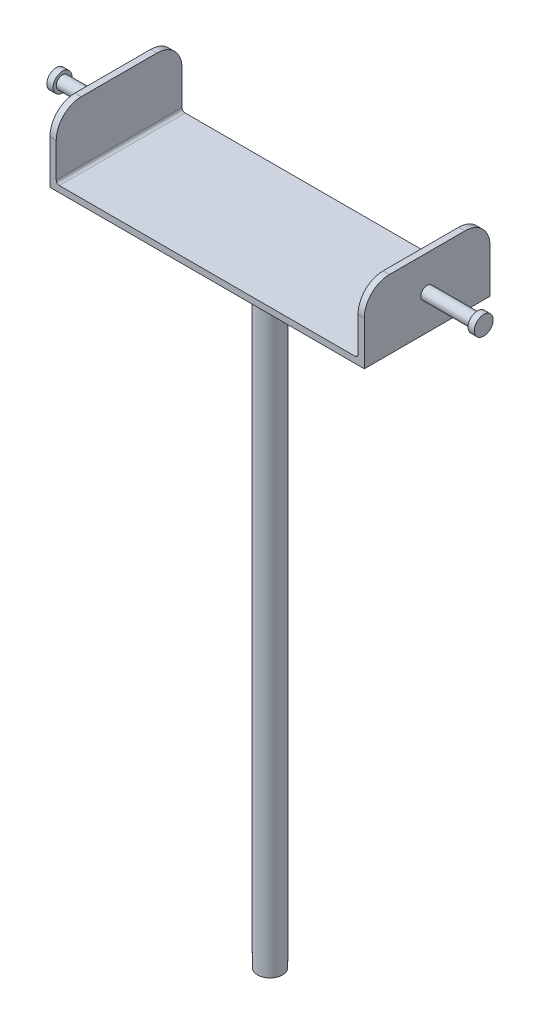
SolidWorks part; units mm, degrees
material "1060 Alloy"
ref_plane "Front Plane" through (0, 0, 0) normal (0, 0, 1) x (1, 0, 0)
ref_plane "Top Plane" through (0, 0, 0) normal (0, 1, 0) x (1, 0, 0)
ref_plane "Right Plane" through (0, 0, 0) normal (1, 0, 0) x (0, 0, -1)
sketch "Sketch1" plane through (0, 0, 0) normal (0, 1, 0) x (1, 0, 0)
  line L0 (-125, 50) -> (125, -50) construction
  line L1 (-125, 50) -> (125, 50)
  line L2 (-125, 50) -> (-125, -50)
  line L3 (-125, -50) -> (125, -50)
  line L4 (125, 50) -> (125, -50)
  dimension "D1" = 250
  dimension "D2" = 100
extrude "Boss-Extrude1" add sketch "Sketch1" along normal blind 5
sketch "Sketch2" plane through (0, 5, 0) normal (0, 1, 0) x (1, 0, 0)
  line L0 (-125, -50) -> (125, -50) construction
  line L1 (-125, 50) -> (-120, 50)
  line L2 (-125, 50) -> (-125, -50)
  line L3 (-125, -50) -> (-120, -50)
  line L4 (-120, 50) -> (-120, -50)
  line L5 (0, 50) -> (0, 56.6385) construction
  line L6 (125, 50) -> (-125, 50) construction
  line L7 (120, 50) -> (120, -50)
  line L8 (125, -50) -> (120, -50)
  line L9 (125, 50) -> (125, -50)
  line L10 (125, 50) -> (120, 50)
  dimension "D1" = 5
extrude "Boss-Extrude2" add sketch "Sketch2" along normal blind 50
fillet "Fillet1" radius 20 4 edges at (122.5, 55, -50) (122.5, 55, 50) (-122.5, 55, -50) (-122.5, 55, 50)
sketch "Sketch3" plane through (-125, 0, 0) normal (-1, 0, 0) x (0, 0, 1)
  line L0 (0, 55) -> (0, 0) construction
  line L1 (-30, 55) -> (30, 55) construction
  line L2 (-50, 0) -> (50, 0) construction
  circle A0 centre (0, 27.5) radius 5
  dimension "D1" = 10
extrude "Boss-Extrude3" add sketch "Sketch3" against normal blind 40 from surface starting at face at (125, 31.3807, 0)
extrude "Boss-Extrude4" add sketch "Sketch3<2>" along normal blind 40
sketch "Sketch3<2>" plane through (-125, 0, 0) normal (-1, 0, 0) x (0, 0, 1) same geometry as "Sketch3"
sketch "Sketch4" plane through (0, 0, 0) normal (0, -1, 0) x (-1, 0, 0)
  line L0 (125, -50) -> (-125, 50) construction
  circle A0 centre (0, 0) radius 10
  dimension "D1" = 20
extrude "Boss-Extrude5" add sketch "Sketch4" along normal blind 500
sketch "Sketch6" plane through (165, 0, 0) normal (1, 0, 0) x (0, 0, -1)
  circle A0 centre (0, 27.5) radius 7.5
  dimension "D1" = 15
extrude "Boss-Extrude9" add sketch "Sketch6" along normal blind 5
sketch "Sketch7" plane through (-165, 0, 0) normal (-1, 0, 0) x (0, 0, 1)
  circle A0 centre (0, 27.5) radius 7.5
  dimension "D1" = 15
extrude "Boss-Extrude11" add sketch "Sketch7" along normal blind 5
fillet "Fillet3" radius 2.5 2 edges at (120, 5, 0)
